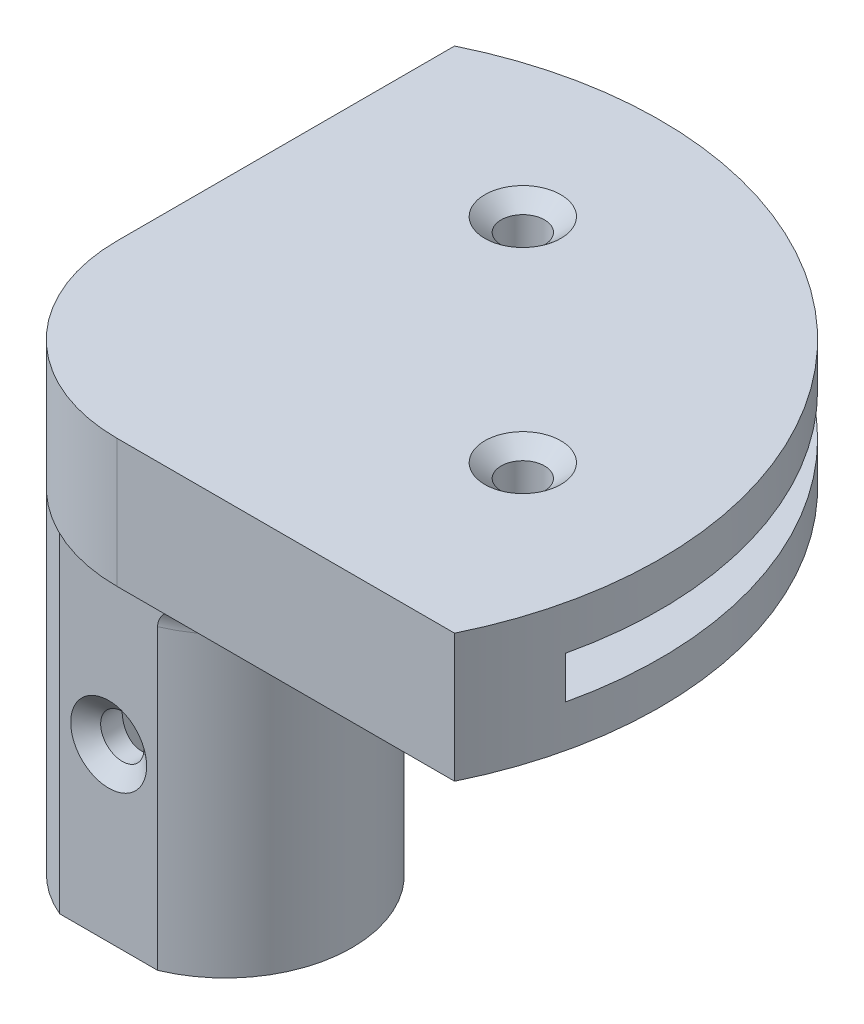
SolidWorks part; units mm, degrees
other "Camera1"
other "Camera2"
material "ABS"
ref_plane "Front Plane" through (0, 0, 0) normal (0, 0, 1) x (1, 0, 0)
ref_plane "Top Plane" through (0, 0, 0) normal (0, 1, 0) x (1, 0, 0)
ref_plane "Right Plane" through (0, 0, 0) normal (1, 0, 0) x (0, 0, -1)
sketch "Sketch2" plane through (0, 0, 0) normal (0, 1, 0) x (1, 0, 0)
  line L0 (-6.1346, -10.9507) -> (1.2352, -10.9507)
  line L1 (-6.1346, 6.6161) -> (1.2352, 6.6161)
  arc A0 (-6.1346, 6.6161) -> (-6.1346, -10.9507) centre (-2.4496, -2.1673) ccw
  circle A1 centre (-2.4496, -2.1673) radius 6.35
  arc A2 (1.2352, -10.9507) -> (1.2352, 6.6161) centre (-2.4496, -2.1673) ccw
  point P0 (-11.9404, -2.9741)
  point P1 (-9.7575, -8.2765)
  dimension "D1" = 12.7
sketch "Sketch3" plane through (0, 0, 0) normal (0, 1, 0) x (1, 0, 0)
  line L0 (0.0818, -12.8507) -> (25.4818, -12.8507)
  line L1 (-12.7876, 0.0187) -> (-12.7876, 25.4187)
  line L2 (-6.6277, -6.6908) -> (-6.6277, 27.5993)
  line L3 (-6.6277, -6.6908) -> (27.6625, -6.6908)
  line L4 (20.0088, 19.9456) -> (-9.0182, -9.0814) construction
  arc A0 (-12.7876, 0.0187) -> (0.0818, -12.8507) centre (0.0818, 0.0187) ccw
  arc A1 (25.4818, -12.8507) -> (-12.7876, 25.4187) centre (-0.2222, -0.2854) ccw
  point P0 (-9.0182, -9.0814)
  point P2 (20.0088, 19.9456)
  point P17 (-10.1818, -7.7452)
  dimension "D1" = 6.1599
extrude "Boss-Extrude1" add sketch "Sketch3" along normal blind 3.175 contours L0 A1 L1 A0
sketch "Sketch5" plane through (0, 3.175, 0) normal (0, 1, 0) x (1, 0, 0)
  line L0 (-6.6277, -6.6908) -> (-6.6277, 27.5993) construction
  line L1 (-6.6277, -6.6908) -> (27.6625, -6.6908) construction
  line L2 (0.0818, -12.8507) -> (25.4818, -12.8507)
  line L3 (-12.7876, 25.4187) -> (-12.7876, 0.0187)
  line L4 (0.0818, -12.8507) -> (25.4818, -12.8507)
  line L5 (-12.7876, 25.4187) -> (-12.7876, 0.0187)
  line L6 (-6.6277, -6.6908) -> (-6.6277, 27.5993)
  line L7 (-6.6277, -6.6908) -> (27.6625, -6.6908)
  arc A2 (25.4818, -12.8507) -> (-12.7876, 25.4187) centre (-0.2222, -0.2854) ccw
  arc A3 (-12.7876, 0.0187) -> (0.0818, -12.8507) centre (0.0818, 0.0187) ccw
  arc A4 (25.4818, -12.8507) -> (-12.7876, 25.4187) centre (-0.2222, -0.2854) ccw
  arc A5 (-12.7876, 0.0187) -> (0.0818, -12.8507) centre (0.0818, 0.0187) ccw
  dimension "D1" = 0
extrude "Boss-Extrude2" add sketch "Sketch5" along normal blind 3.175 contours L5 A5 L4 A4 L7 L6
ref_plane "Plane3" through (0, 6.35, 0) normal (0, 1, 0) x (1, 0, 0)
sketch "Sketch6" plane through (0, 6.35, 0) normal (0, 1, 0) x (1, 0, 0)
  line L0 (-12.7876, 25.4187) -> (-12.7876, 0.0187) construction
  line L1 (0.0818, -12.8507) -> (25.4818, -12.8507) construction
  line L2 (-12.7876, 25.4187) -> (-12.7876, 0.0187)
  line L3 (0.0818, -12.8507) -> (25.4818, -12.8507)
  arc A0 (-6.6277, 27.5993) -> (-12.7876, 25.4187) centre (-0.2222, -0.2854) ccw construction
  arc A1 (27.6625, -6.6908) -> (-6.6277, 27.5993) centre (-0.2222, -0.2854) ccw construction
  arc A2 (-12.7876, 0.0187) -> (0.0818, -12.8507) centre (0.0818, 0.0187) ccw construction
  arc A3 (25.4818, -12.8507) -> (27.6625, -6.6908) centre (-0.2222, -0.2854) ccw construction
  arc A4 (-6.6277, 27.5993) -> (-12.7876, 25.4187) centre (-0.2222, -0.2854) ccw
  arc A5 (27.6625, -6.6908) -> (-6.6277, 27.5993) centre (-0.2222, -0.2854) ccw
  arc A6 (-12.7876, 0.0187) -> (0.0818, -12.8507) centre (0.0818, 0.0187) ccw
  arc A7 (25.4818, -12.8507) -> (27.6625, -6.6908) centre (-0.2222, -0.2854) ccw
extrude "Boss-Extrude3" add sketch "Sketch6" along normal blind 3.302
extrude "Boss-Extrude4" add sketch "Sketch2" against normal blind 25.4
sketch "Sketch28" plane through (0, 0, 0) normal (0, -1, 0) x (-1, 0, 0)
  arc A0 (9.7575, -8.2765) -> (12.7876, 0.0187) centre (-0.0818, 0.0187) ccw construction
  point P0 (9.7575, -8.2765)
ref_plane "Plane4" through (0, 9.652, 0) normal (0, 1, 0) x (1, 0, 0)
hole_wizard "CSK for #4 Flat Head Machine Screw (100)3" positions "Sketch12" profile "Sketch11" countersink size "#4" standard "ANSI Inch"
sketch "Sketch12" plane through (0, 9.652, 0) normal (0, 1, 0) x (1, 0, 0)
  line L0 (16.9343, 0.8332) -> (16.9343, -12.8507) construction
  line L1 (0.0818, -12.8507) -> (25.4818, -12.8507) construction
  line L3 (0.8964, 16.8711) -> (-12.7876, 16.8711) construction
  line L4 (-12.7876, 25.4187) -> (-12.7876, 0.0187) construction
  line L6 (-6.6277, -6.6908) -> (20.0088, 19.9456) construction
  line L8 (0.8964, 16.8711) -> (16.9343, 0.8332) construction
  arc A1 (25.4818, -12.8507) -> (-12.7876, 25.4187) centre (-0.2222, -0.2854) ccw construction
  point P0 (16.9343, 0.8332)
  point P2 (0.8964, 16.8711)
sketch "Sketch11" plane through (16.9343, 9.652, -0.8332) normal (1, 0, 0) x (0, 0, 1)
  line L0 (0, 0) -> (0, 3.302)
  line L1 (0, 3.302) -> (1.6319, 3.302)
  line L2 (1.6319, 3.302) -> (1.6319, 1.0284)
  line L3 (1.6319, 1.0284) -> (2.8575, 0)
  line L5 (2.8575, 0) -> (0, 0)
  line L6 (-1.6319, 1.0284) -> (-2.8575, 0) construction
  line L11 (0, -6.35) -> (0, 107.95) construction
  dimension "Thru Hole Dia." = 3.2639
  dimension "Thru Hole Depth" = 3.302
  dimension "Near C'Sink Dia." = 5.715
  dimension "Near C'Sink Angle" = 100
ref_plane "Plane6" through (0, 0, 0) normal (0, -1, 0) x (-1, 0, 0)
sketch "Sketch20" plane through (0, 0, 0) normal (0, -1, 0) x (-1, 0, 0)
  line L2 (12.7876, 0.0187) -> (12.7876, 25.4187)
  line L3 (-25.4818, -12.8507) -> (-0.0818, -12.8507)
  line L4 (12.7876, 0.0187) -> (12.7876, 25.4187)
  line L5 (-25.4818, -12.8507) -> (-0.0818, -12.8507)
  line L8 (-1.2352, 6.6161) -> (6.1346, 6.6161)
  line L9 (-1.2352, 6.6161) -> (6.1346, 6.6161)
  line L10 (6.1346, -10.9507) -> (-1.2352, -10.9507)
  line L11 (6.1346, -10.9507) -> (-1.2352, -10.9507)
  arc A2 (12.7876, 25.4187) -> (-25.4818, -12.8507) centre (0.2222, -0.2854) ccw
  arc A3 (-0.0818, -12.8507) -> (9.5582, -8.5072) centre (-0.0818, 0.0187) ccw
  arc A4 (12.7876, 25.4187) -> (-25.4818, -12.8507) centre (0.2222, -0.2854) ccw
  arc A5 (-0.0818, -12.8507) -> (9.5582, -8.5072) centre (-0.0818, 0.0187) ccw
  arc A10 (9.7575, -8.2765) -> (6.1346, 6.6161) centre (2.4496, -2.1673) ccw
  arc A11 (9.7575, -8.2765) -> (6.1346, 6.6161) centre (2.4496, -2.1673) ccw
  arc A12 (9.7575, -8.2765) -> (12.7876, 0.0187) centre (-0.0818, 0.0187) ccw
  arc A13 (9.7575, -8.2765) -> (12.7876, 0.0187) centre (-0.0818, 0.0187) ccw
  arc A14 (6.1346, -10.9507) -> (9.5582, -8.5072) centre (2.4496, -2.1673) ccw
  arc A15 (6.1346, -10.9507) -> (9.5582, -8.5072) centre (2.4496, -2.1673) ccw
  arc A16 (-1.2352, 6.6161) -> (-1.2352, -10.9507) centre (2.4496, -2.1673) ccw
  arc A17 (-1.2352, 6.6161) -> (-1.2352, -10.9507) centre (2.4496, -2.1673) ccw
  spline S40 degree 3 poles (9.1886, 6.95) (9.1886, 13.3) (9.1886, 19.65) (9.1886, 26.0037) knots 0 0 0 0 1 1 1 1
  spline S41 degree 3 poles (9.1886, 26.0037) (2.8416, 26.0037) (-3.5069, 26.0037) (-9.8614, 26.0037) knots 1 1 1 1 2 2 2 2
  spline S42 degree 3 poles (-9.8614, 26.0037) (-9.8614, 19.655) (-9.8614, 13.3025) (-9.8614, 6.95) knots 2 2 2 2 3 3 3 3
  spline S43 degree 3 poles (-9.8614, 6.95) (-3.5147, 6.95) (2.8362, 6.95) (9.1886, 6.95) knots 3 3 3 3 4 4 4 4
  spline S45 degree 3 poles (-4.4097, 12.4089) (-4.4097, 15.1294) (-4.4097, 17.8409) (-4.4097, 20.5552) knots 11 11 11 11 12 12 12 12
  spline S47 degree 3 poles (6.4555, 12.393) (6.4555, 11.4766) (6.4555, 10.5801) (6.4555, 9.6858) knots 6 6 6 6 7 7 7 7
  spline S60 degree 3 poles (6.4543, 23.2729) (6.4543, 22.3643) (6.4543, 21.4678) (6.4543, 20.5646) knots 2 2 2 2 3 3 3 3
  spline S62 degree 3 poles (3.7419, 20.5646) (3.742, 17.8408) (3.742, 15.1169) (3.7421, 12.393) knots 4 4 4 4 5 5 5 5
  spline S64 degree 3 poles (3.7471, 23.2729) (4.6635, 23.2729) (5.56, 23.2729) (6.4543, 23.2729) knots 1 1 1 1 2 2 2 2
  spline S66 degree 3 poles (6.4543, 20.5646) (5.5414, 20.5646) (4.6417, 20.5646) (3.7419, 20.5646) knots 3 3 3 3 4 4 4 4
  spline S68 degree 3 poles (3.7471, 20.5595) (3.7471, 21.4635) (3.7471, 22.3676) (3.7471, 23.2729) knots 0 0 0 0 1 1 1 1
  spline S70 degree 3 poles (3.7472, 9.6858) (3.7472, 10.5987) (3.7472, 11.4985) (3.7472, 12.3982) knots 8 8 8 8 9 9 9 9
  spline S72 degree 3 poles (6.4555, 9.6858) (5.5468, 9.6858) (4.6504, 9.6858) (3.7472, 9.6858) knots 7 7 7 7 8 8 8 8
  spline S74 degree 3 poles (3.7421, 12.393) (4.6461, 12.393) (5.5502, 12.393) (6.4555, 12.393) knots 5 5 5 5 6 6 6 6
  spline S76 degree 3 poles (3.7472, 12.3982) (1.05, 12.3973) (-1.6473, 12.3965) (-4.3446, 12.3962) (-4.3669, 12.3962) (-4.3892, 12.4047) (-4.4097, 12.4089) knots 9 9 9 9 10 10 10 11 11 11 11
  spline S78 degree 3 poles (-4.4097, 20.5552) (-4.3738, 20.5583) (-4.3502, 20.562) (-4.3266, 20.562) (-1.6354, 20.5613) (1.0558, 20.5604) (3.7471, 20.5595) knots 12 12 12 12 13 13 13 14 14 14 14
  point P1 (5.6098, 24.2883)
  point P2 (3.7471, 23.2729)
  point P13 (3.7471, 23.2729)
  dimension "D1" = 0
extrude "Cut-Extrude7" cut sketch "Sketch20" against normal blind 2 contours S68 S66 S60 S64 | S78 S45 S76 S62 | S74 S70 S72 S47 | S41 S42 S43 S40
hole_wizard "CSK for #4 Flat Head Machine Screw (100)2" positions "Sketch26" profile "Sketch25" countersink size "#4" standard "ANSI Inch"
sketch "Sketch26" plane through (0, 0, 10.9507) normal (0, 0, 1) x (1, 0, 0)
  line L0 (-2.4497, -25.4) -> (-2.4497, 0.3858) construction
  line L1 (-6.1346, -25.4) -> (1.2352, -25.4) construction
  point P0 (-2.4497, -12.5071)
sketch "Sketch25" plane through (-2.4497, -12.5071, 10.9507) normal (1, 0, 0) x (0, -1, 0)
  line L0 (0, 0) -> (0, 10.9806)
  line L1 (0, 10.9806) -> (1.6319, 10)
  line L2 (1.6319, 10) -> (1.6319, 1.0284)
  line L3 (1.6319, 1.0284) -> (2.8575, 0)
  line L5 (2.8575, 0) -> (0, 0)
  line L6 (-1.6319, 1.0284) -> (-2.8575, 0) construction
  line L10 (0, 10.9806) -> (-1.6319, 10) construction
  line L11 (0, -6.35) -> (0, 107.95) construction
  dimension "Hole Dia." = 3.2639
  dimension "Hole Depth" = 10
  dimension "Near C'Sink Dia." = 5.715
  dimension "Near C'Sink Angle" = 100
  dimension "Drill Angle" = 118
fillet "Fillet1" radius 3 2 edges at (7.0754, 0, 2.1673)
